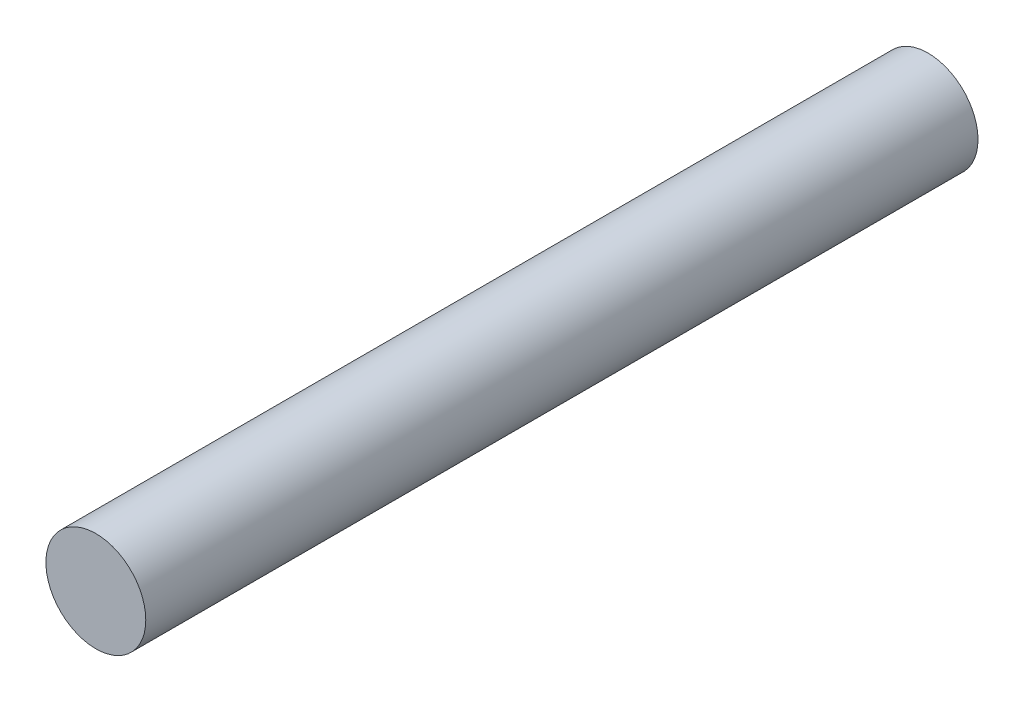
SolidWorks part; units mm, degrees
ref_plane "Front Plane" through (0, 0, 0) normal (0, 0, 1) x (1, 0, 0)
ref_plane "Top Plane" through (0, 0, 0) normal (0, 1, 0) x (1, 0, 0)
ref_plane "Right Plane" through (0, 0, 0) normal (1, 0, 0) x (0, 0, -1)
sketch "Sketch1" plane through (0, 0, 0) normal (0, 0, 1) x (1, 0, 0)
  circle A0 centre (0, 0) radius 3
  dimension "D1" = 6
extrude "Boss-Extrude1" add sketch "Sketch1" along normal blind 50
